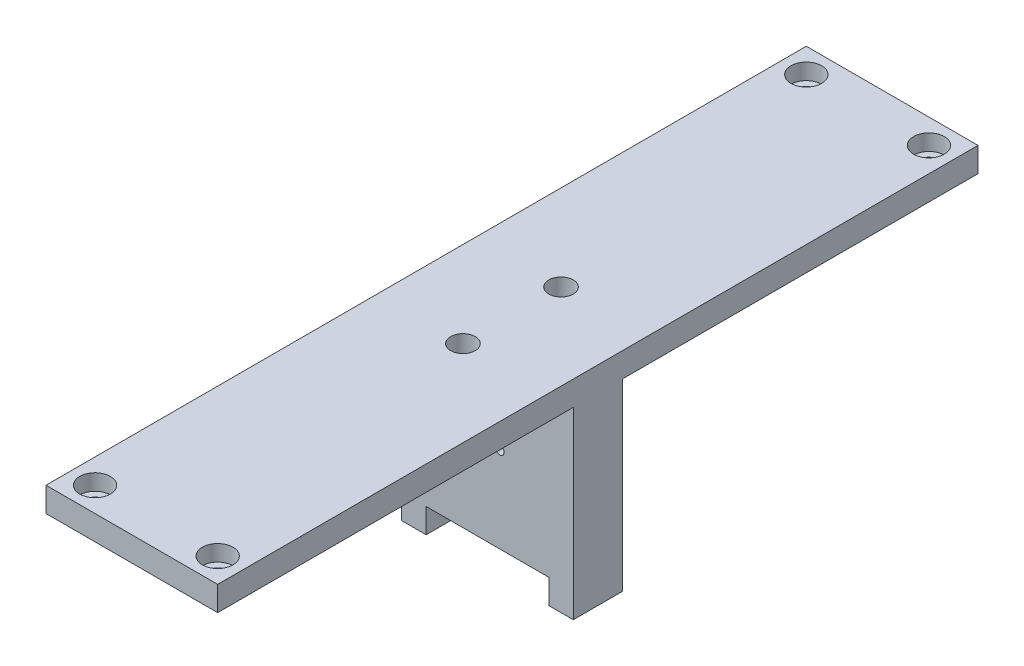
SolidWorks part; units mm, degrees
material "6061 Alloy"
ref_plane "Front Plane" through (0, 0, 0) normal (0, 0, 1) x (1, 0, 0)
ref_plane "Top Plane" through (0, 0, 0) normal (0, 1, 0) x (1, 0, 0)
ref_plane "Right Plane" through (0, 0, 0) normal (1, 0, 0) x (0, 0, -1)
sketch "Sketch1" plane through (0, 0, 0) normal (0, 1, 0) x (1, 0, 0)
  line L1 (-22.225, -98.425) -> (22.225, -98.425)
  line L2 (-22.225, -98.425) -> (-22.225, 98.425)
  line L3 (-22.225, 98.425) -> (22.225, 98.425)
  line L4 (22.225, -98.425) -> (22.225, 98.425)
  line L5 (-22.225, -98.425) -> (22.225, 98.425) construction
  line L6 (-22.225, 98.425) -> (22.225, -98.425) construction
  point P0 (0, 0)
  dimension "D1" = 196.85
  dimension "D2" = 44.45
extrude "Boss-Extrude1" add sketch "Sketch1" along normal blind 6.35
sketch "Sketch2" plane through (0, 0, 0) normal (0, -1, 0) x (-1, 0, 0)
  line L0 (-22.225, -98.425) -> (-22.225, 98.425) construction
  line L1 (22.225, 6.35) -> (-22.225, 6.35)
  line L2 (22.225, 6.35) -> (22.225, -6.35)
  line L3 (22.225, -6.35) -> (-22.225, -6.35)
  line L4 (-22.225, 6.35) -> (-22.225, -6.35)
  line L5 (22.225, 6.35) -> (-22.225, -6.35) construction
  line L6 (22.225, -6.35) -> (-22.225, 6.35) construction
  point P0 (0, 0)
  dimension "D1" = 12.7
extrude "Boss-Extrude2" add sketch "Sketch2" along normal blind 47.625
hole_wizard "CBORE for #8 Socket Head Cap Screw1" positions "Sketch4" profile "Sketch5" counterbore size "#8" standard "ANSI Inch" end condition up to next
sketch "Sketch4" plane through (0, 6.35, 0) normal (0, 1, 0) x (1, 0, 0)
  line L0 (-22.225, 98.425) -> (-22.225, -98.425) construction
  line L1 (-22.225, -98.425) -> (22.225, -98.425) construction
  line L2 (22.225, 98.425) -> (-22.225, 98.425) construction
  line L3 (22.225, -98.425) -> (22.225, 98.425) construction
  point P0 (-15.875, -92.075)
  point P2 (15.875, -92.075)
  point P4 (15.875, 92.075)
  point P6 (-15.875, 92.075)
  dimension "D1" = 6.35
  dimension "D2" = 6.35
  dimension "D3" = 6.35
  dimension "D4" = 6.35
  dimension "D5" = 6.35
  dimension "D6" = 6.35
  dimension "D7" = 6.35
  dimension "D8" = 6.35
sketch "Sketch5" plane through (-15.875, 6.35, 92.075) normal (1, 0, 0) x (0, 0, 1)
  line L0 (0, 0) -> (0, 6.35)
  line L1 (0, 6.35) -> (2.1526, 6.35)
  line L3 (2.1526, 6.35) -> (2.1527, 4.1656)
  line L4 (2.1527, 4.1656) -> (3.9687, 4.1656)
  line L5 (3.9687, 4.1656) -> (3.9687, 0)
  line L7 (3.9687, 0) -> (0, 0)
  line L11 (0, -6.35) -> (0, 107.95) construction
  dimension "Thru Hole Dia." = 4.3053
  dimension "Thru Hole Depth" = 6.35
  dimension "C'Bore Dia." = 7.9375
  dimension "C'Bore Depth" = 4.1656
sketch "Sketch6" plane through (0, -47.625, 0) normal (0, -1, 0) x (-1, 0, 0)
  line L0 (22.225, 6.35) -> (-22.225, 6.35) construction
  line L1 (15.875, 6.35) -> (-15.875, 6.35)
  line L2 (15.875, 6.35) -> (15.875, -6.35)
  line L3 (15.875, -6.35) -> (-15.875, -6.35)
  line L4 (-15.875, 6.35) -> (-15.875, -6.35)
  line L5 (-22.225, -6.35) -> (22.225, -6.35) construction
  line L6 (22.225, -6.35) -> (22.225, 6.35) construction
  line L7 (-22.225, 6.35) -> (-22.225, -6.35) construction
  dimension "D1" = 6.35
  dimension "D2" = 6.35
extrude "Cut-Extrude1" cut sketch "Sketch6" against normal blind 6.35
hole_wizard "1/4 (0.25) Diameter Hole1" positions "Sketch7" profile "Sketch8" hole size "1/4" standard "ANSI Inch" end condition through all
sketch "Sketch7" plane through (0, 6.35, 0) normal (0, 1, 0) x (1, 0, 0)
  point P0 (0, 12.7)
  point P2 (0, -12.7)
  dimension "D1" = 12.7
  dimension "D2" = 12.7
sketch "Sketch8" plane through (0, 6.35, -12.7) normal (1, 0, 0) x (0, 0, 1)
  line L0 (0, 0) -> (0, 53.975)
  line L1 (0, 53.975) -> (3.175, 53.975)
  line L2 (3.175, 53.975) -> (3.175, 0)
  line L5 (3.175, 0) -> (0, 0)
  line L11 (0, -6.35) -> (0, 107.95) construction
  dimension "Thru Hole Dia." = 6.35
  dimension "Thru Hole Depth" = 53.975
hole_wizard "#4-40 Tapped Hole1" positions "Sketch9" profile "Sketch10" tap size "#4-40" standard "ANSI Inch" end condition through all
sketch "Sketch9" plane through (0, 0, 6.35) normal (0, 0, 1) x (1, 0, 0)
  line L0 (-22.225, 6.35) -> (22.225, 6.35) construction
  point P0 (-3.175, -19.05)
  point P2 (3.175, -19.05)
  dimension "D1" = 6.35
  dimension "D2" = 3.175
  dimension "D3" = 25.4
sketch "Sketch10" plane through (-3.175, -19.05, 6.35) normal (1, 0, 0) x (0, -1, 0)
  line L0 (0, 0) -> (0, 104.775)
  line L1 (0, 104.775) -> (1.1303, 104.775)
  line L2 (1.1303, 104.775) -> (1.1303, 0)
  line L5 (1.1303, 0) -> (0, 0)
  line L11 (0, -6.35) -> (0, 107.95) construction
  dimension "Thru Tap Drill Dia." = 2.2606
  dimension "Thru Tap Drill Depth" = 104.775
cosmetic thread "Hole Thread1"
cosmetic thread "Hole Thread2"
